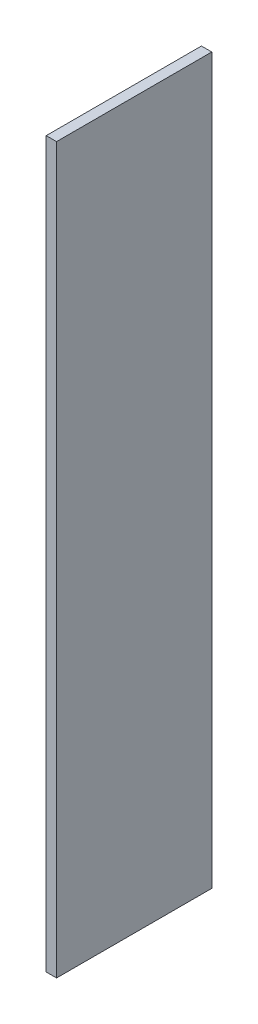
SolidWorks part; units mm, degrees
ref_plane "Front Plane" through (0, 0, 0) normal (0, 0, 1) x (1, 0, 0)
ref_plane "Top Plane" through (0, 0, 0) normal (0, 1, 0) x (1, 0, 0)
ref_plane "Right Plane" through (0, 0, 0) normal (1, 0, 0) x (0, 0, -1)
sketch "Sketch1" plane through (0, 0, 0) normal (0, 0, 1) x (1, 0, 0)
  line L1 (0, 0) -> (0.2, 0)
  line L2 (0, 0) -> (0, 14)
  line L3 (0, 14) -> (0.2, 14)
  line L4 (0.2, 0) -> (0.2, 14)
  dimension "D2" = 0.2
extrude "Boss-Extrude1" add sketch "Sketch1" along normal blind 3
equation "\"A.L\"= 0.07m"
equation "\"A.h\"= 0.007m"
equation "\"A.d\"= 0.003m"
equation "\"A.delta\"= 45.0001"
equation "\"A.w\"= 0.02m"
equation "\"A.v\"= 0.03m"
equation "\"A.s\"= 0.014m"
equation "\"A.t\"= 0.007m"
equation "\"B.L\"= 0.065m"
equation "\"B.h\"= 0.008m"
equation "\"B.s\"= 0.016m"
equation "\"B.t\"= 0.008m"
equation "\"C.h\"= 0.0065m"
equation "\"C.d\"= 0.003m"
equation "\"C.L\"= 0.05m"
equation "\"C.wmax\"= 0.005m"
equation "\"D.L\"= 0.06m"
equation "\"D.h\"= 0.008m"
equation "\"D.s\"= 0.012m"
equation "\"D.t\"= 0.008m"
equation "\"a_h\"= 0.0002m"
equation "\"a_d\"= 0.003m"
equation "\"a_L\"= 0.008m"
equation "\"b_h\"= 0.0004m"
equation "\"b_d\"= 0.003m"
equation "\"b_L\"= 0.007m"
equation "\"c_h\"= 0.0001m"
equation "\"c_d\"= 0.003m"
equation "\"c_L\"= 0.01m"
equation "\"d_h\"= 0.0001m"
equation "\"d_d\"= 0.003m"
equation "\"d_L\"= 0.01m"
equation "\"S.h\"= 0.015m"
equation "\"S.L\"= 0.09075m"
equation "\"D1@Sketch1\"=\"a_L\"+0.006"
equation "\"D2@Sketch1\"=\"a_h\""
equation "\"D1@Boss-Extrude1\"=\"a_d\""
